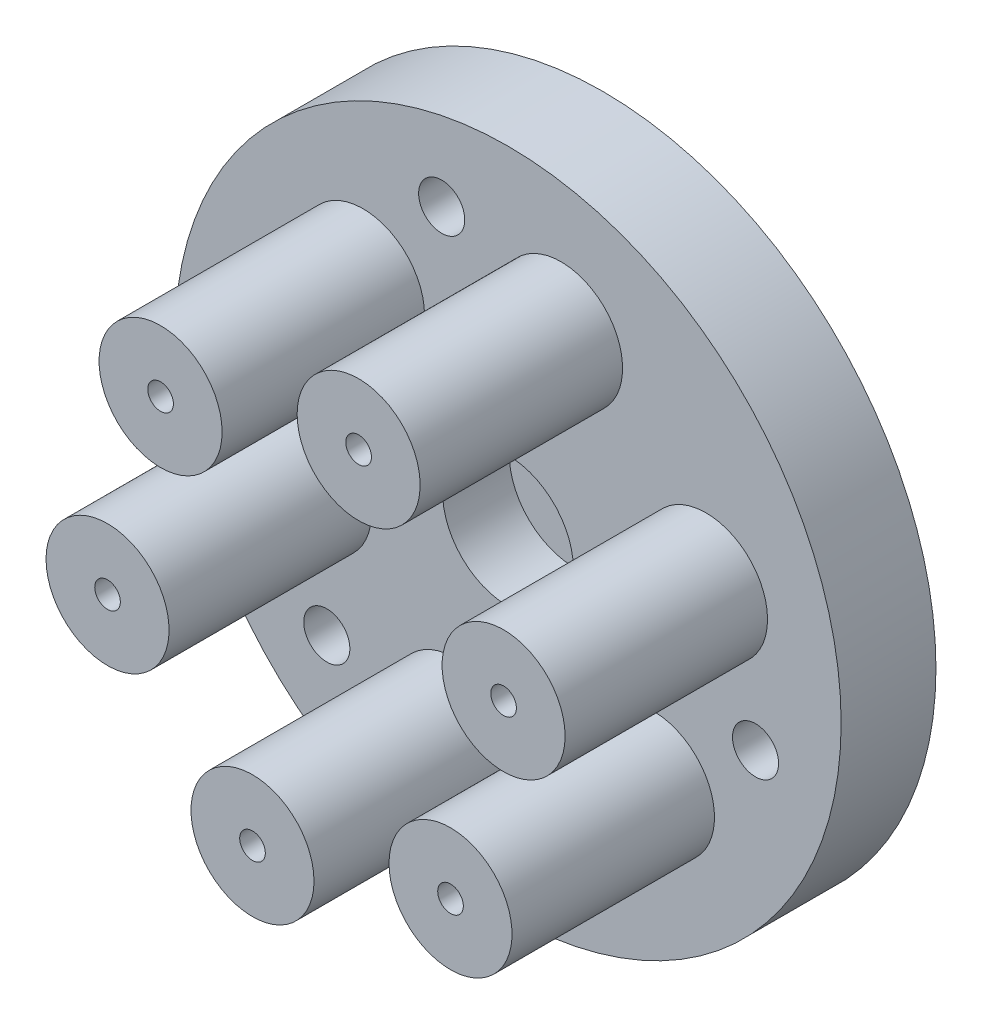
SolidWorks part; units mm, degrees
ref_plane "前视基准面" through (0, 0, 0) normal (0, 0, 1) x (1, 0, 0)
ref_plane "上视基准面" through (0, 0, 0) normal (0, 1, 0) x (1, 0, 0)
ref_plane "右视基准面" through (0, 0, 0) normal (1, 0, 0) x (0, 0, -1)
other "Configuration Table"
sketch "草图1" plane through (0, 0, 0) normal (0, 0, 1) x (1, 0, 0)
  circle A0 centre (0, 0) radius 13
  dimension "D1" = 26
extrude "凸台-拉伸1" add sketch "草图1" along normal blind 3.7 contours A0
sketch "草图3" plane through (0, 0, 3.7) normal (0, 0, 1) x (1, 0, 0)
  line L0 (0, 0) -> (0, 10.0172) construction
  line L1 (-5.6569, 5.6569) -> (0, 0) construction
  circle A0 centre (-5.6569, 5.6569) radius 2.4
  circle A1 centre (-5.6569, 5.6569) radius 0.5
  dimension "D1" = 4.8
  dimension "D3" = 1
  dimension "D2" = 8
  dimension "D4" = 45
extrude "凸台-拉伸3" add sketch "草图3" along normal blind 7.9
pattern_circular "阵列(圆周)1" count 6 over 360 about axis through (0, 0, 3.7) along (0, 0, -1) of "凸台-拉伸3"
sketch "草图4" plane through (0, 0, 3.7) normal (0, 0, 1) x (1, 0, 0)
  line L0 (0, 0) -> (-2.5882, 9.6593) construction
  line L1 (-2.5882, 9.6593) -> (-5.6569, 5.6569) construction
  line L2 (-5.6569, 5.6569) -> (2.0706, 7.7274) construction
  line L3 (2.0706, 7.7274) -> (-2.5882, 9.6593) construction
  circle A0 centre (-2.5882, 9.6593) radius 0.9
  circle A1 centre (-5.6569, 5.6569) radius 0.5 construction
  circle A2 centre (2.0706, 7.7274) radius 0.5 construction
  dimension "D2" = 1.8
  dimension "D1" = 10
extrude "切除-拉伸1" cut sketch "草图4" against normal through all
pattern_circular "阵列(圆周)2" count 3 over 360 about axis through (0, 0, 3.7) along (0, 0, -1) of "切除-拉伸1" reverse direction yes
sketch "草图5" plane through (0, 0, 3.7) normal (0, 0, 1) x (1, 0, 0)
  circle A0 centre (0, 0) radius 2.55
  circle A1 centre (0, 0) radius 1.1
  dimension "D1" = 2.2
  dimension "D2" = 5.1
extrude "切除-拉伸2" cut sketch "草图5" against normal through all contours A1
extrude "切除-拉伸3" cut sketch "草图5<4>" against normal blind 2.6
sketch "草图5<4>" plane through (0, 0, 3.7) normal (0, 0, 1) x (1, 0, 0) same geometry as "草图5"
